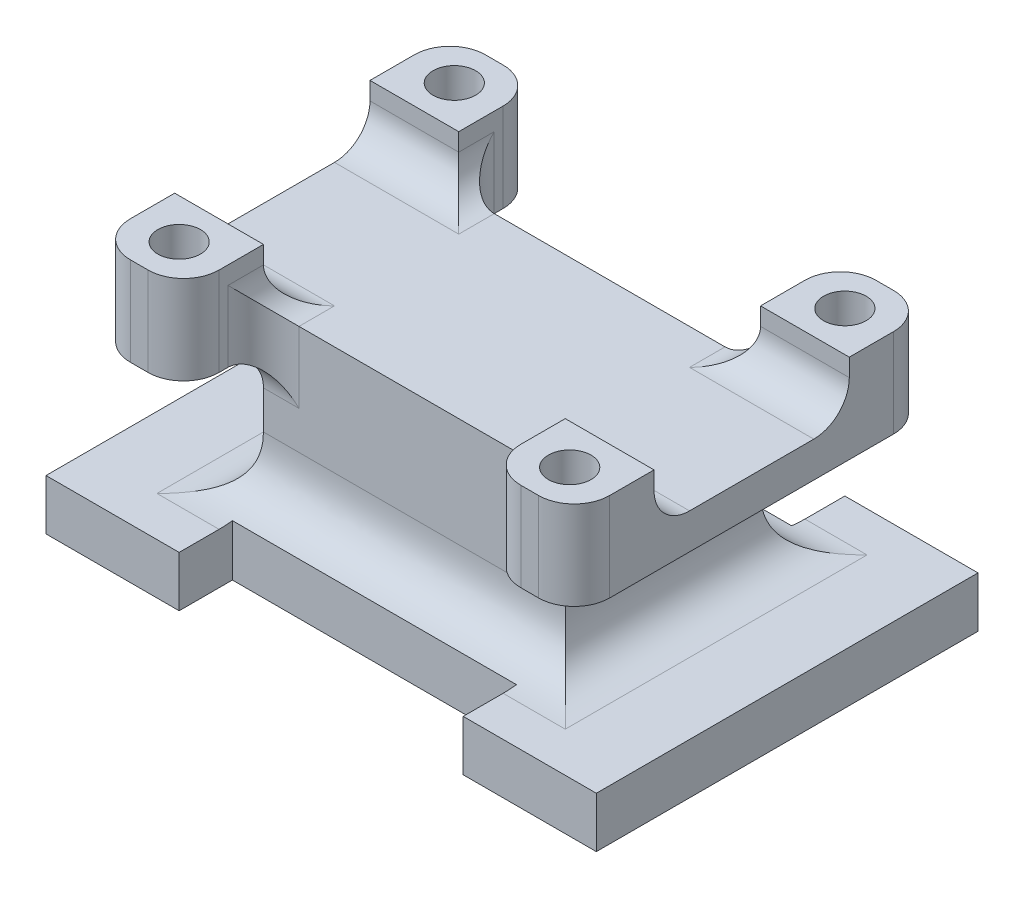
SolidWorks part; units mm, degrees
material "Esun Hard Tough Resin"
ref_plane "Front Plane" through (0, 0, 0) normal (0, 0, 1) x (1, 0, 0)
ref_plane "Top Plane" through (0, 0, 0) normal (0, 1, 0) x (1, 0, 0)
ref_plane "Right Plane" through (0, 0, 0) normal (1, 0, 0) x (0, 0, -1)
sketch "Sketch1" plane through (0, 0, 0) normal (0, 1, 0) x (1, 0, 0)
  line L0 (8, 10.75) -> (15.5, 10.75)
  line L1 (-15.5, -10.75) -> (-8, -10.75)
  line L2 (-15.5, -10.75) -> (-15.5, 10.75)
  line L3 (-15.5, 10.75) -> (-8, 10.75)
  line L4 (15.5, -10.75) -> (15.5, 10.75)
  line L5 (-15.5, -10.75) -> (15.5, 10.75) construction
  line L6 (-15.5, 10.75) -> (15.5, -10.75) construction
  line L8 (8, 10.75) -> (8, 7.75)
  line L9 (8, 7.75) -> (-8, 7.75)
  line L10 (-8, 10.75) -> (-8, 7.75)
  line L12 (8, -10.75) -> (8, -7.75)
  line L13 (8, -7.75) -> (-8, -7.75)
  line L14 (-8, -10.75) -> (-8, -7.75)
  line L15 (8, -10.75) -> (15.5, -10.75)
  point P0 (0, 0)
  point P14 (0, 7.75)
  point P15 (0, -7.75)
  dimension "D1" = 21.5
  dimension "D2" = 31
  dimension "D3" = 3
  dimension "D4" = 16
extrude "Boss-Extrude1" add sketch "Sketch1" along normal blind 2.85
sketch "Sketch2" plane through (0, 2.85, 0) normal (0, 1, 0) x (1, 0, 0)
  line L1 (-8.5, -5.5) -> (8.5, -5.5)
  line L2 (-8.5, -5.5) -> (-8.5, 5.5)
  line L3 (-8.5, 5.5) -> (8.5, 5.5)
  line L4 (8.5, -5.5) -> (8.5, 5.5)
  line L5 (-8.5, -5.5) -> (8.5, 5.5) construction
  line L6 (-8.5, 5.5) -> (8.5, -5.5) construction
  point P0 (0, 0)
  dimension "D1" = 11
  dimension "D2" = 17
extrude "Boss-Extrude2" add sketch "Sketch2" along normal blind 7.15
sketch "Sketch3" plane through (0, 10, 0) normal (0, 1, 0) x (1, 0, 0)
  line L0 (-11, 7.75) -> (11, 7.75) construction
  line L1 (-8.5, -5.5) -> (8.5, -5.5)
  line L2 (-8.5, -5.5) -> (-8.5, 5.5)
  line L3 (-8.5, 5.5) -> (8.5, 5.5)
  line L4 (8.5, -5.5) -> (8.5, 5.5)
  line L5 (-8.5, -5.5) -> (8.5, 5.5) construction
  line L6 (-8.5, 5.5) -> (8.5, -5.5) construction
  line L7 (-13.5, 10) -> (-8.5, 10)
  line L8 (-13.5, 10) -> (-13.5, -10)
  line L9 (-13.5, -10) -> (-8.5, -10)
  line L10 (-8.5, 10) -> (-8.5, -10)
  line L11 (8.5, 10) -> (13.5, 10)
  line L12 (8.5, 10) -> (8.5, -10)
  line L13 (8.5, -10) -> (13.5, -10)
  line L14 (13.5, 10) -> (13.5, -10)
  line L15 (-11, 7.75) -> (-11, -7.75) construction
  circle A0 centre (-11, 7.75) radius 1.2
  circle A1 centre (11, 7.75) radius 1.2
  circle A2 centre (-11, -7.75) radius 1.2
  circle A3 centre (11, -7.75) radius 1.2
  point P0 (0, 0)
  point P14 (-8.5, 0)
  point P15 (-8.5, 0)
  point P16 (8.5, 0)
  point P17 (8.5, 0)
  point P27 (0, 7.75)
  point P28 (0, 5.5)
  point P30 (-11, 0)
  line M19 (8.5, -5.5) -> (8.5, 5.5)
  line M20 (8.5, 5.5) -> (-8.5, 5.5)
  line M21 (-8.5, 5.5) -> (-8.5, -5.5)
  line M22 (-8.5, -5.5) -> (8.5, -5.5)
  dimension "D7" = 2.4
  dimension "D1" = 17
  dimension "D2" = 11
  dimension "D3" = 4.5
  dimension "D4" = 5
  dimension "D5" = 22
  dimension "D6" = 15.5
extrude "Boss-Extrude3" add sketch "Sketch3" along normal blind 5 contours L10 L7 L8 L9 A2 A0 M21 | M22 M19 M20 M21 | L14 L11 L12 L13 A3 A1 M19 region at (0, 10, 0) region at (-11, 10, 0) region at (11, 10, 0)
sketch "Sketch4" plane through (0, 15, 0) normal (0, 1, 0) x (1, 0, 0)
  line L0 (-13.5, 5.5) -> (13.5, 5.5) construction
  line L1 (-13.5, 10) -> (-13.5, -10) construction
  line L2 (13.5, 10) -> (13.5, -10) construction
  line L3 (8.5, 5.5) -> (-8.5, 5.5) construction
  line L4 (-13.5, -5.5) -> (13.5, -5.5) construction
  line L5 (-8.5, -5.5) -> (8.5, -5.5) construction
  line L7 (-13.5, 5.5) -> (13.5, 5.5)
  line L8 (-13.5, 5.5) -> (-13.5, -5.5)
  line L9 (-13.5, -5.5) -> (13.5, -5.5)
  line L10 (13.5, 5.5) -> (13.5, -5.5)
extrude "Cut-Extrude1" cut sketch "Sketch4" against normal blind 3
fillet "Fillet1" radius 2 12 edges at (-13.5, 12.5, 10) (-8.5, 12.5, 10) (8.5, 12.5, 10) (13.5, 12.5, 10) (-11, 12, 5.5) (11, 12, 5.5) (-11, 12, -5.5) (11, 12, -5.5) (-13.5, 12.5, -10) (-8.5, 12.5, -10) (8.5, 12.5, -10) (13.5, 12.5, -10)
fillet "Fillet2" radius 2 8 edges at (8.5, 12, -4.5) (8.5, 11, -5.5) (-8.5, 12, -4.5) (-8.5, 11, -5.5) (-8.5, 12, 4.5) (8.5, 12, 4.5) (8.5, 11, 5.5) (-8.5, 11, 5.5)
fillet "Fillet3" radius 2 4 edges at (-7.5, 10, -5.5) (-7.5, 10, 5.5) (7.5, 10, 5.5) (7.5, 10, -5.5)
fillet "Fillet4" radius 3 4 edges at (8.5, 2.85, 0) (-8.5, 2.85, 0) (0, 2.85, 5.5) (0, 2.85, -5.5) conic radius 2
